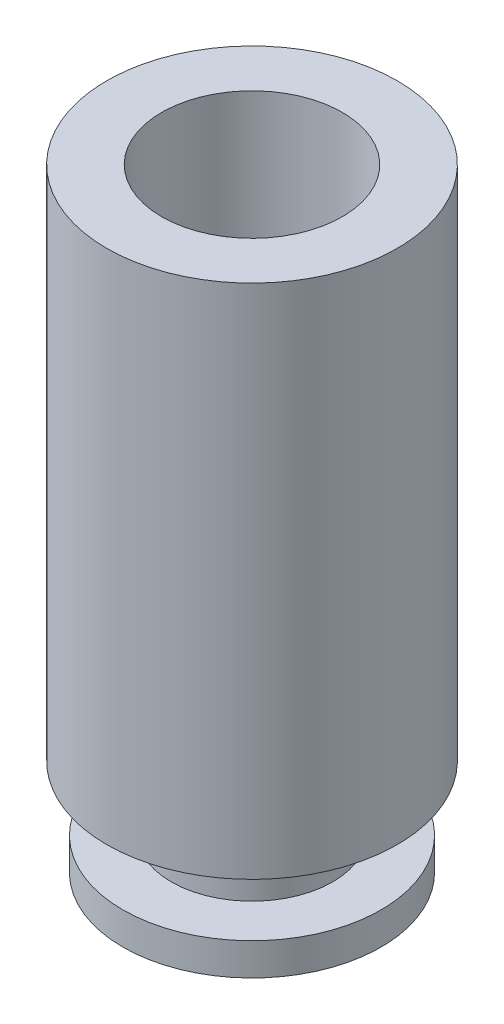
SolidWorks part; units mm, degrees
ref_plane "Front Plane" through (0, 0, 0) normal (0, 0, 1) x (1, 0, 0)
ref_plane "Top Plane" through (0, 0, 0) normal (0, 1, 0) x (1, 0, 0)
ref_plane "Right Plane" through (0, 0, 0) normal (1, 0, 0) x (0, 0, -1)
sketch "Sketch1" plane through (0, 0, 0) normal (0, 1, 0) x (1, 0, 0)
  circle A0 centre (-0.522, 0.5111) radius 1.375
  circle A1 centre (-0.522, 0.5111) radius 2.25
  dimension "D1" = 2.75
  dimension "D2" = 4.5
extrude "Boss-Extrude1" add sketch "Sketch1" along normal blind 8 contours A1
extrude "Boss-Extrude2" add sketch "Sketch1<3>" along normal blind 1 contours A0 region at (-0.522, 0, -0.5111)
sketch "Sketch1<3>" plane through (0, 0, 0) normal (0, 1, 0) x (1, 0, 0) same geometry as "Sketch1"
sketch "Sketch5" plane through (0, 0, 0) normal (0, -1, 0) x (1, 0, 0)
  circle A3 centre (-0.522, -0.5111) radius 1.25
  dimension "D1" = 2.5
extrude "Boss-Extrude3" add sketch "Sketch5" along normal blind 1 contours A3
sketch "Sketch6" plane through (0, -1, 0) normal (0, -1, 0) x (1, 0, 0)
  circle A0 centre (-0.522, -0.5111) radius 2
  dimension "D1" = 4
extrude "Boss-Extrude4" add sketch "Sketch6" along normal blind 0.5
sketch "Sketch8" plane through (0, -1.5, 0) normal (0, -1, 0) x (-1, 0, 0)
  circle A0 centre (0.522, 0.5111) radius 1.5
  dimension "D1" = 3
sketch "Sketch11" plane through (0, 8, 0) normal (0, 1, 0) x (1, 0, 0)
  text T0 "VIII" font "Century Gothic" height in points 5
sketch "Sketch12" plane through (0, 8, 0) normal (0, 1, 0) x (1, 0, 0)
  circle A0 centre (-0.522, 0.5111) radius 1.4
  dimension "D1" = 2.8
extrude "Cut-Extrude1" cut sketch "Sketch12" against normal blind 7.5
